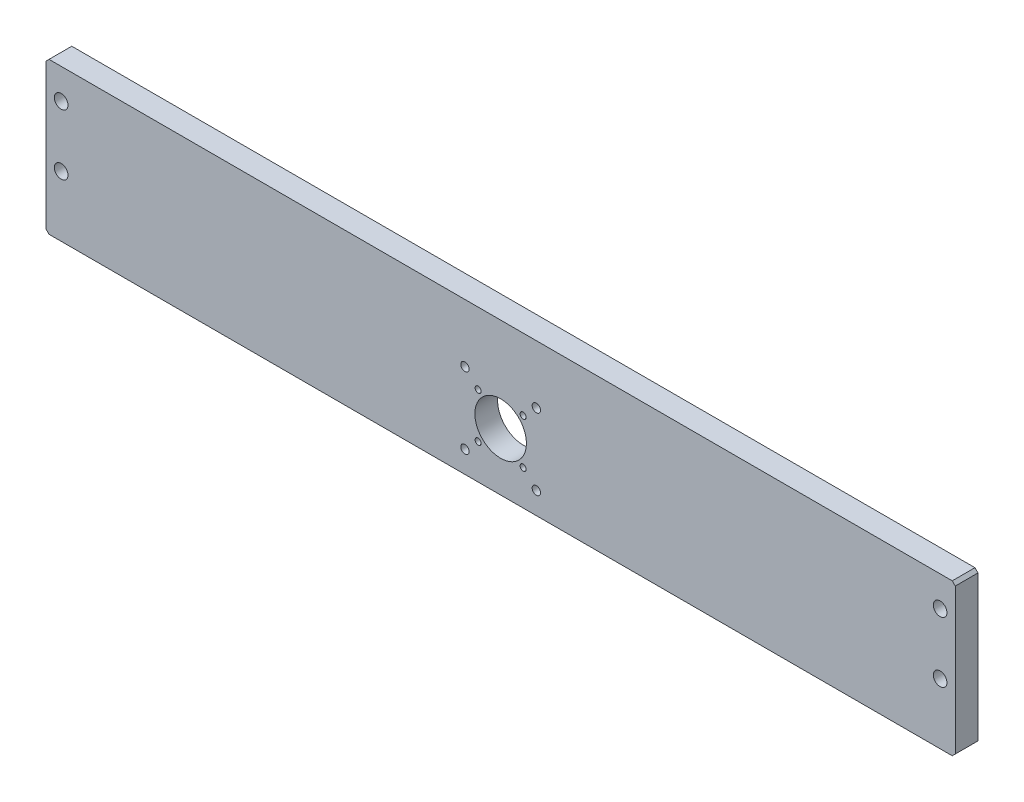
SolidWorks part; units mm, degrees
ref_plane "Piano frontale" through (0, 0, 0) normal (0, 0, 1) x (1, 0, 0)
ref_plane "Piano superiore" through (0, 0, 0) normal (0, 1, 0) x (1, 0, 0)
ref_plane "Piano destro" through (0, 0, 0) normal (1, 0, 0) x (0, 0, -1)
sketch "Schizzo1" plane through (0, 0, 0) normal (0, 0, 1) x (1, 0, 0)
  line L0 (300, 100) -> (300, 0) construction
  line L1 (2, 0) -> (598, 0)
  line L2 (0, 2) -> (0, 98)
  line L3 (2, 100) -> (598, 100)
  line L4 (600, 2) -> (600, 98)
  line L6 (384.4715, 38) -> (198.6179, 38) construction
  line L7 (300, 38) -> (318.5099, 38) construction
  line L9 (300, 38) -> (280.51, 57.49) construction
  line L21 (0, 98) -> (2, 100)
  line L22 (2, 0) -> (0, 2)
  line L23 (598, 0) -> (600, 2)
  line L24 (598, 100) -> (600, 98)
  circle A0 centre (300, 38) radius 17
  circle A1 centre (300, 38) radius 21 construction
  circle A2 centre (314.8492, 52.8492) radius 2
  circle A3 centre (314.8492, 23.1508) radius 2
  circle A4 centre (285.1508, 23.1508) radius 2
  circle A13 centre (285.1508, 52.8492) radius 2
  point P0 (0, 0)
  point P1 (600, 100)
  point P2 (0, 100)
  point P3 (600, 0)
  point P9 (285.1508, 52.8492)
  point P13 (285.1508, 52.8492)
  point P18 (323.57, 61.57)
  point P19 (276.43, 61.57)
  point P21 (276.43, 14.43)
  point P23 (323.57, 14.43)
  dimension "D4" = 34
  dimension "D17" = 4
  dimension "D8" = 45
  dimension "D5" = 42
  dimension "D1" = 100
  dimension "D2" = 600
  dimension "D3" = 38
  dimension "D6" = 23.57
  dimension "D7" = 23.57
extrude "Boss-Extrude1" add sketch "Schizzo1" against normal blind 15
sketch "Sketch2" plane through (0, 0, 0) normal (0, -1, 0) x (1, 0, 0)
  line L0 (2, -7.5) -> (598, -7.5) construction
  line L1 (2, -15) -> (2, 0) construction
  line L2 (598, -15) -> (598, 0) construction
  line L3 (300, -15) -> (300, 0) construction
  line L4 (2, -15) -> (598, -15) construction
  line L5 (321, 0) -> (279, 0) construction
  line L6 (0, -15) -> (0, 0) construction
  point P12 (30, -7.5)
  point P15 (570, -7.5)
  dimension "D1" = 30
hole_wizard "M8 Tapped Hole1" positions "3DSketch1" profile "Sketch3" tap size "M8" standard "ISO"
sketch3d "3DSketch1"
  point P0 (30, 0, -7.5)
  point P3 (570, 0, -7.5)
sketch "Sketch3" plane through (30, 0, -7.5) normal (1, 0, 0) x (0, 0, -1)
  line L0 (0, 0) -> (0, 25.7929)
  line L1 (0, 25.7929) -> (3.4, 23.75)
  line L2 (3.4, 23.75) -> (3.4, 0)
  line L5 (3.4, 0) -> (0, 0)
  line L10 (0, 25.7929) -> (-3.4, 23.75) construction
  line L11 (0, -6.35) -> (0, 107.95) construction
  dimension "Tap Drill Dia." = 6.8
  dimension "Tap Drill Depth" = 23.75
  dimension "Drill Angle" = 118
sketch "Sketch8" plane through (0, 0, -15) normal (0, 0, -1) x (-1, 0, 0)
  line L0 (-590, 100) -> (-590, 0) construction
  line L1 (-2, 100) -> (-598, 100) construction
  line L2 (-2, 0) -> (-598, 0) construction
  line L3 (-600, 2) -> (-600, 98) construction
  line L4 (-300, 100) -> (-300, 0) construction
  point P8 (-590, 80)
  point P9 (-590, 40)
  point P14 (-10, 40)
  point P15 (-10, 80)
  dimension "D1" = 10
  dimension "D2" = 20
  dimension "D3" = 40
hole_wizard "CBORE for M8 Hex Socket Head Cap Screw1" positions "3DSketch2" profile "Sketch9" counterbore size "M8" standard "ISO"
sketch3d "3DSketch2"
  point P0 (590, 80, -15)
  point P3 (590, 40, -15)
  point P6 (10, 80, -15)
  point P9 (10, 40, -15)
sketch "Sketch9" plane through (590, 80, -15) normal (1, 0, 0) x (0, 1, 0)
  line L0 (0, 0) -> (0, 25.75)
  line L1 (0, 25.75) -> (4.5, 25.75)
  line L2 (4.5, 25.75) -> (4.5, 8.6)
  line L3 (4.5, 8.6) -> (7.5, 8.6)
  line L4 (7.5, 8.6) -> (7.5, 0)
  line L5 (7.5, 0) -> (0, 0)
  line L10 (0, 25.75) -> (-4.5, 25.75) construction
  line L11 (0, -6.35) -> (0, 107.95) construction
  dimension "Hole Dia." = 9
  dimension "Hole Depth" = 25.75
  dimension "C'Bore Dia." = 15
  dimension "C'Bore Depth" = 8.6
  dimension "Drill Angle" = 180
hole_wizard "M5 Clearance Hole1" positions "Sketch12" profile "Sketch11" hole size "M5" standard "ISO"
sketch "Sketch12" plane through (0, 0, 0) normal (0, 0, 1) x (1, 0, 0)
  point P0 (276.43, 61.57)
  point P3 (323.57, 61.57)
  point P6 (323.57, 14.43)
  point P9 (276.43, 14.43)
sketch "Sketch11" plane through (276.43, 61.57, 0) normal (1, 0, 0) x (0, -1, 0)
  line L0 (0, 0) -> (0, 36.6524)
  line L1 (0, 36.6524) -> (2.75, 35)
  line L2 (2.75, 35) -> (2.75, 0)
  line L5 (2.75, 0) -> (0, 0)
  line L10 (0, 36.6524) -> (-2.75, 35) construction
  line L11 (0, -6.35) -> (0, 107.95) construction
  dimension "Hole Dia." = 5.5
  dimension "Hole Depth" = 35
  dimension "Drill Angle" = 118
